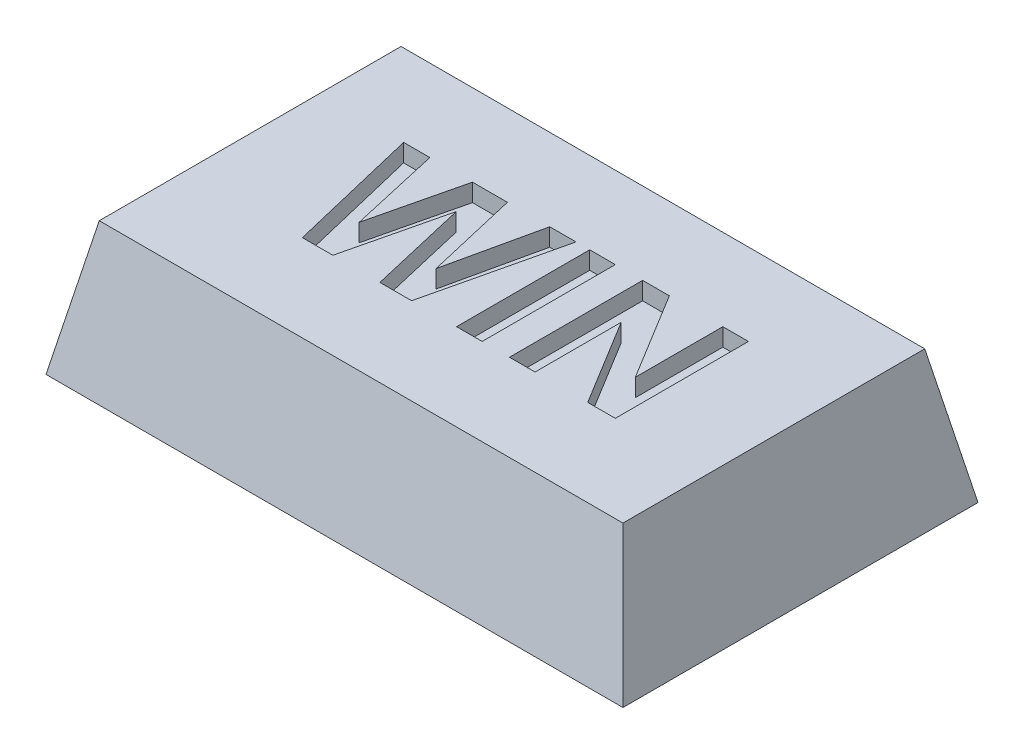
SolidWorks part; units mm, degrees
ref_plane "Front Plane" through (0, 0, 0) normal (0, 0, 1) x (1, 0, 0)
ref_plane "Top Plane" through (0, 0, 0) normal (0, 1, 0) x (1, 0, 0)
ref_plane "Right Plane" through (0, 0, 0) normal (1, 0, 0) x (0, 0, -1)
sketch "Sketch1" plane through (0, 0, 0) normal (0, 1, 0) x (1, 0, 0)
  line L1 (0, 0) -> (13, 0)
  line L2 (0, 0) -> (0, 8)
  line L3 (0, 8) -> (13, 8)
  line L4 (13, 0) -> (13, 8)
  dimension "D1" = 8
  dimension "D2" = 13
extrude "Boss-Extrude1" add sketch "Sketch1" along normal blind 3
sketch "Sketch2" plane through (0, 0, 0) normal (0, 0, 1) x (1, 0, 0)
  line L0 (0, 0) -> (0.6, 3)
  line L1 (0, 3) -> (13, 3) construction
  line L2 (0.6, 3) -> (0, 3)
  line L3 (0, 3) -> (0, 0)
  line L4 (13, 0) -> (12.4, 3)
  line L5 (12.4, 3) -> (13, 3)
  line L6 (13, 3) -> (13, 0)
  dimension "D1" = 0.6
  dimension "D2" = 0.6
extrude "Cut-Extrude1" cut sketch "Sketch2" against normal through all both and the other way through all
sketch "Sketch3" plane through (0, 0, 0) normal (1, 0, 0) x (0, 0, -1)
  line L0 (0, 0) -> (0.6, 3)
  line L1 (8, 3) -> (0, 3) construction
  line L2 (0.6, 3) -> (0, 3)
  line L3 (0, 3) -> (0, 0)
  line L4 (8, 3) -> (7.4, 3)
  line L5 (7.4, 3) -> (8, 0)
  line L6 (8, 3) -> (8, 0)
  dimension "D1" = 0.6
  dimension "D2" = 0.6
extrude "Cut-Extrude2" cut sketch "Sketch3" along normal through all both and the other way through all
sketch "Sketch4" plane through (0, 0, 0) normal (0, -1, 0) x (1, 0, 0)
  line L1 (6.5, 0) -> (6.5, -8) construction
  line L2 (13, -8) -> (0, -8) construction
  line L3 (0, 0) -> (13, 0) construction
  circle A0 centre (6.5, -3.75) radius 1.75
  dimension "D1" = 3.5
  dimension "D2" = 0
  dimension "D3" = 3.75
extrude "Cut-Extrude3" cut sketch "Sketch4" against normal blind 0.4
sketch "Sketch5" plane through (0, 0, 0) normal (0, -1, 0) x (1, 0, 0)
  line L5 (0, 0) -> (13, 0) construction
  line L6 (2.5, -8) -> (10.5, -8)
  line L7 (2.5, -8) -> (2.5, -6.9)
  line L8 (2.5, -6.9) -> (10.5, -6.9)
  line L9 (10.5, -8) -> (10.5, -6.9)
  point P2 (6.5, 0)
  dimension "D1" = 1.1
  dimension "D2" = 4
  dimension "D3" = 4
extrude "Boss-Extrude2" add sketch "Sketch5" along normal blind 2
fillet "Fillet1" radius 4 2 edges at (10.5, -2, -7.45) (2.5, -2, -7.45)
sketch "Sketch6" plane through (0, 3, 0) normal (0, 1, 0) x (1, 0, 0)
  text T0 "WIN" font "Arial" height 3
extrude "Cut-Extrude4" cut sketch "Sketch6" against normal blind 0.4
